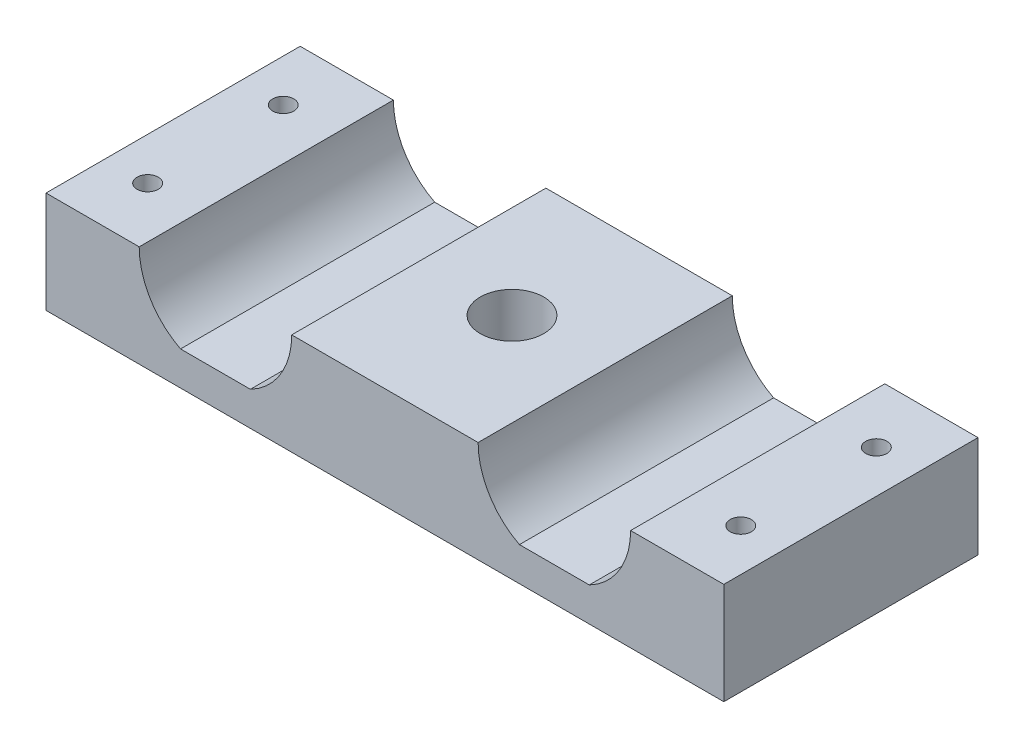
SolidWorks part; units mm, degrees
ref_plane "Front Plane" through (0, 0, 0) normal (0, 0, 1) x (1, 0, 0)
ref_plane "Top Plane" through (0, 0, 0) normal (0, 1, 0) x (1, 0, 0)
ref_plane "Right Plane" through (0, 0, 0) normal (1, 0, 0) x (0, 0, -1)
sketch "Sketch1" plane through (0, 0, 0) normal (0, 0, 1) x (1, 0, 0)
  line L0 (-50.8, 0) -> (50.8, 0)
  line L1 (50.8, 0) -> (50.8, 15.24)
  line L2 (50.8, 15.24) -> (36.83, 15.24)
  line L3 (25.4, 15.24) -> (51.7323, 15.24) construction
  line L4 (13.97, 15.24) -> (-13.97, 15.24)
  line L5 (30.6363, 5.08) -> (20.1637, 5.08)
  line L6 (0, 0) -> (0, 35.6145) construction
  line L7 (-25.4, 15.24) -> (-51.7323, 15.24) construction
  line L8 (-30.6363, 5.08) -> (-20.1637, 5.08)
  line L9 (-50.8, 15.24) -> (-36.83, 15.24)
  line L10 (-50.8, 0) -> (-50.8, 15.24)
  arc A0 (13.97, 15.24) -> (20.1637, 5.08) centre (25.4, 15.24) ccw
  arc A1 (30.6363, 5.08) -> (36.83, 15.24) centre (25.4, 15.24) ccw
  arc A2 (-30.6363, 5.08) -> (-36.83, 15.24) centre (-25.4, 15.24) cw
  arc A3 (-13.97, 15.24) -> (-20.1637, 5.08) centre (-25.4, 15.24) cw
  point P6 (0, 0)
  point P13 (0, 22.0146)
  point P20 (0, 15.24)
  dimension "D1" = 22.86
  dimension "D2" = 10.16
  dimension "D3" = 15.24
  dimension "D4" = 25.4
  dimension "D5" = 50.8
extrude "Boss-Extrude1" add sketch "Sketch1" along normal blind 38.1
hole_wizard "Hole1" positions "Sketch2" profile "Sketch3" legacy
sketch "Sketch2" plane through (0, 15.24, 0) normal (0, 1, 0) x (1, 0, 0)
  point P0 (0, -19.05)
  point P3 (0, 0)
  point P5 (0, 0)
  dimension "D1" = 19.05
sketch "Sketch3" plane through (0, 15.24, 19.05) normal (1, 0, 0) x (0, 0, 1)
  line L0 (0, 0) -> (0, 101.6)
  line L1 (0, 101.6) -> (4.7625, 101.6)
  line L2 (4.7625, 101.6) -> (4.7625, 0)
  line L3 (4.7625, 0) -> (0, 0)
  line L4 (0, 110) -> (0, -10) construction
  dimension "Diameter" = 9.525
  dimension "Depth" = 101.6
hole_wizard "Hole2" positions "Sketch4" profile "Sketch5" legacy
sketch "Sketch4" plane through (0, 15.24, 0) normal (0, 1, 0) x (1, 0, 0)
  point P0 (-44.45, -8.89)
  dimension "D1" = 44.45
  dimension "D2" = 8.89
sketch "Sketch5" plane through (-44.45, 15.24, 8.89) normal (1, 0, 0) x (0, 0, 1)
  line L0 (0, 0) -> (0, 101.6)
  line L1 (0, 101.6) -> (1.5875, 101.6)
  line L2 (1.5875, 101.6) -> (1.5875, 0)
  line L3 (1.5875, 0) -> (0, 0)
  line L4 (0, 110) -> (0, -10) construction
  dimension "Diameter" = 3.175
  dimension "Depth" = 101.6
pattern_linear "LPattern1" count 2 spacing 20.32 along (0, 0, 1) count 2 spacing 88.9 along (1, 0, 0) of "Hole2"
